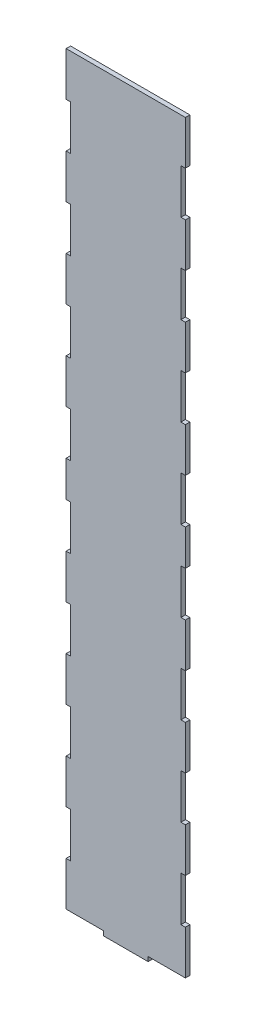
SolidWorks part; units mm, degrees
ref_plane "Plano frontal" through (0, 0, 0) normal (0, 0, 1) x (1, 0, 0)
ref_plane "Plano superior" through (0, 0, 0) normal (0, 1, 0) x (1, 0, 0)
ref_plane "Plano direito" through (0, 0, 0) normal (1, 0, 0) x (0, 0, -1)
sketch "Esboço1" plane through (0, 0, 0) normal (0, 0, 1) x (1, 0, 0)
  line L0 (15, -250) -> (40, -250)
  line L1 (-40, -250) -> (-15, -250)
  line L2 (-40, -250) -> (-40, 250)
  line L3 (-40, 250) -> (40, 250)
  line L4 (40, -250) -> (40, 250)
  line L5 (-40, -250) -> (40, 250) construction
  line L6 (-40, 250) -> (40, -250) construction
  line L8 (-15, -250) -> (-15, -253)
  line L9 (-15, -253) -> (15, -253)
  line L10 (15, -250) -> (15, -253)
  point P0 (0, 0)
  dimension "D1" = 500
  dimension "D2" = 80
  dimension "D3" = 3
  dimension "D4" = 30
  dimension "D5" = 25
extrude "Ressalto-extrusão1" add sketch "Esboço1" along normal blind 3
sketch "Esboço2" plane through (0, 0, 3) normal (0, 0, 1) x (1, 0, 0)
  line L0 (-40, 0) -> (40, 0) construction
  line L5 (-40, 250) -> (-40, -250) construction
  line L6 (-40, 220.5) -> (-37, 220.5)
  line L7 (-40, 220.5) -> (-40, 190.5)
  line L8 (-40, 190.5) -> (-37, 190.5)
  line L9 (-37, 220.5) -> (-37, 190.5)
  line L10 (40, 250) -> (-40, 250) construction
  line L11 (-40, 101.5) -> (-37, 101.5)
  line L12 (-40, 161) -> (-37, 161)
  line L13 (-40, 161) -> (-40, 131)
  line L14 (-40, 131) -> (-37, 131)
  line L15 (-37, 161) -> (-37, 131)
  line L16 (-40, 101.5) -> (-40, 71.5)
  line L17 (-40, 71.5) -> (-37, 71.5)
  line L18 (-37, 101.5) -> (-37, 71.5)
  line L19 (-40, 42) -> (-37, 42)
  line L20 (-40, 42) -> (-40, 12)
  line L21 (-40, 12) -> (-37, 12)
  line L22 (-37, 42) -> (-37, 12)
  line L23 (40, -250) -> (40, 250) construction
  line L24 (-40, -190.5) -> (-37, -190.5)
  line L25 (-37, -220.5) -> (-37, -190.5)
  line L26 (-40, -220.5) -> (-37, -220.5)
  line L27 (-40, -220.5) -> (-40, -190.5)
  line L28 (-40, -131) -> (-37, -131)
  line L29 (-37, -161) -> (-37, -131)
  line L30 (-40, -161) -> (-37, -161)
  line L31 (-40, -161) -> (-40, -131)
  line L32 (-40, -71.5) -> (-37, -71.5)
  line L33 (-37, -101.5) -> (-37, -71.5)
  line L34 (-40, -101.5) -> (-37, -101.5)
  line L35 (-40, -101.5) -> (-40, -71.5)
  line L36 (-40, -12) -> (-37, -12)
  line L37 (-37, -42) -> (-37, -12)
  line L38 (-40, -42) -> (-37, -42)
  line L39 (-40, -42) -> (-40, -12)
  line L40 (0, -253) -> (0, 250) construction
  line L42 (40, -220.5) -> (40, -190.5)
  line L43 (40, -220.5) -> (37, -220.5)
  line L44 (37, -220.5) -> (37, -190.5)
  line L45 (40, -190.5) -> (37, -190.5)
  line L46 (40, -161) -> (40, -131)
  line L47 (40, -161) -> (37, -161)
  line L48 (37, -161) -> (37, -131)
  line L49 (40, -131) -> (37, -131)
  line L50 (40, -101.5) -> (40, -71.5)
  line L51 (40, -101.5) -> (37, -101.5)
  line L52 (37, -101.5) -> (37, -71.5)
  line L53 (40, -71.5) -> (37, -71.5)
  line L54 (40, -42) -> (40, -12)
  line L55 (40, -42) -> (37, -42)
  line L56 (37, -42) -> (37, -12)
  line L57 (40, -12) -> (37, -12)
  line L58 (40, 12) -> (37, 12)
  line L59 (37, 42) -> (37, 12)
  line L60 (40, 42) -> (37, 42)
  line L61 (40, 42) -> (40, 12)
  line L62 (40, 71.5) -> (37, 71.5)
  line L63 (37, 101.5) -> (37, 71.5)
  line L64 (40, 101.5) -> (37, 101.5)
  line L65 (40, 101.5) -> (40, 71.5)
  line L66 (40, 131) -> (37, 131)
  line L67 (37, 161) -> (37, 131)
  line L68 (40, 161) -> (37, 161)
  line L69 (40, 161) -> (40, 131)
  line L70 (40, 190.5) -> (37, 190.5)
  line L71 (37, 220.5) -> (37, 190.5)
  line L72 (40, 220.5) -> (37, 220.5)
  line L73 (40, 220.5) -> (40, 190.5)
  line L74 (-15, -253) -> (15, -253) construction
  point P12 (-38.5, 190.5)
  dimension "D1" = 3
  dimension "D2" = 30
  dimension "D3" = 29.5
  dimension "D4" = 3
  dimension "D5" = 30
  dimension "D6" = 29.5
  dimension "D7" = 3
  dimension "D8" = 30
  dimension "D9" = 29.5
  dimension "D10" = 3
  dimension "D11" = 29.5
  dimension "D12" = 30
extrude "Corte-extrusão1" cut sketch "Esboço2" against normal through all
